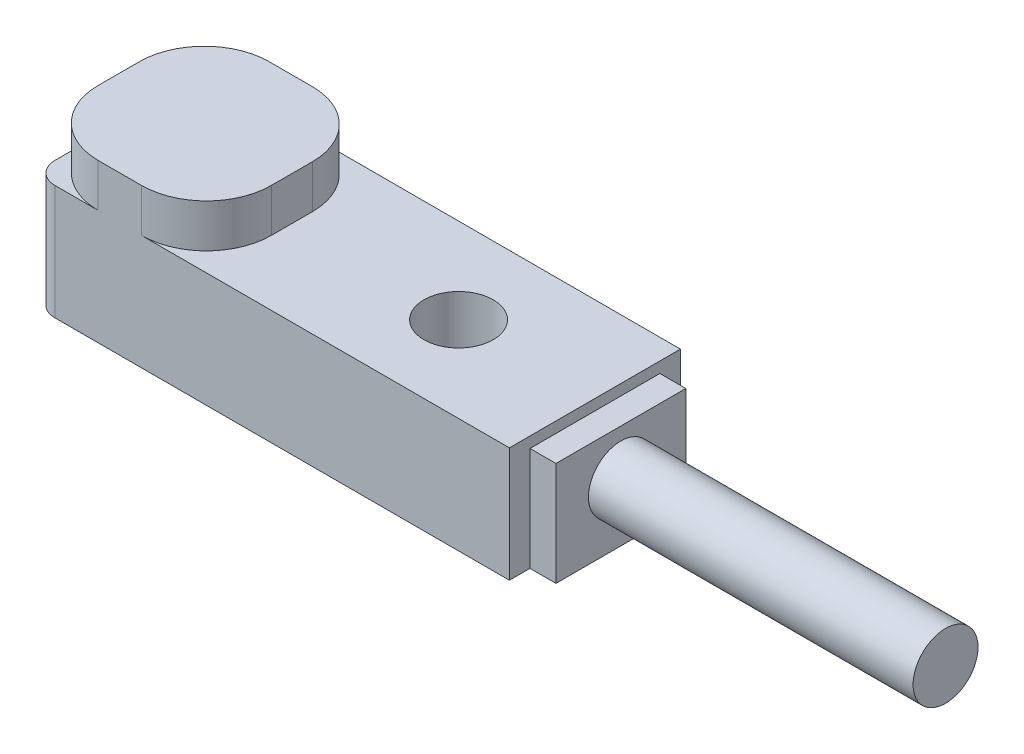
SolidWorks part; units mm, degrees
ref_plane "Plan de face" through (0, 0, 0) normal (0, 0, 1) x (1, 0, 0)
ref_plane "Plan de dessus" through (0, 0, 0) normal (0, 1, 0) x (1, 0, 0)
ref_plane "Plan de droite" through (0, 0, 0) normal (1, 0, 0) x (0, 0, -1)
sketch "Esquisse1" plane through (0, 0, 0) normal (0, 1, 0) x (1, 0, 0)
  line L0 (4, 3.95) -> (18, 3.95)
  line L1 (-4, 3.95) -> (4, 3.95)
  line L2 (-4, 3.95) -> (-4, -3.95)
  line L3 (-4, -3.95) -> (4, -3.95)
  line L4 (4, 3.95) -> (4, -3.95)
  line L5 (18, 3.95) -> (18, -3.95)
  line L6 (18, -3.95) -> (4, -3.95)
  point P4 (-4, 0)
  point P7 (0, 3.95)
  dimension "D1" = 7.9
  dimension "D2" = 8
  dimension "D3" = 22
extrude "Boss.-Extru.1" add sketch "Esquisse1" along normal blind 5.3 contours L6 L5 L0 L4 | L4 L1 L2 L3 region at (0, 0, 0) region at (11, 0, 0)
extrude "Boss.-Extru.2" add sketch "Esquisse1<4>" along normal blind 7.3 contours L4 L1 L2 L3 region at (0, 0, 0)
sketch "Esquisse1<4>" plane through (0, 0, 0) normal (0, 1, 0) x (1, 0, 0) same geometry as "Esquisse1"
sketch "Esquisse2" plane through (0, 7.3, 0) normal (0, 1, 0) x (1, 0, 0)
  line L4 (4, -3.95) -> (4, 3.95)
  line L5 (4, 3.95) -> (-4, 3.95)
  line L6 (-4, 3.95) -> (-4, -3.95)
  line L7 (-4, -3.95) -> (4, -3.95)
  line L8 (4, -0.95) -> (4, 0.95)
  line L9 (1, 3.95) -> (-1, 3.95)
  line L10 (-4, 0.95) -> (-4, -0.95)
  line L11 (-1, -3.95) -> (1, -3.95)
  arc A0 (-4, -0.95) -> (-1, -3.95) centre (-1, -0.95) ccw
  arc A1 (4, -0.95) -> (1, -3.95) centre (1, -0.95) cw
  arc A2 (4, 0.95) -> (1, 3.95) centre (1, 0.95) ccw
  arc A3 (-1, 3.95) -> (-4, 0.95) centre (-1, 0.95) ccw
  dimension "D2" = 3
  dimension "D1" = 0
extrude "Enlèv. mat.-Extru.2" cut sketch "Esquisse2" against normal up to surface (2 mm away) flip side to cut up to face at (11, 5.3, 0)
hole_wizard "Dégagement M31" positions "Esquisse3" profile "Esquisse4" hole size "M3" standard "ISO" end condition through all
sketch "Esquisse3" plane through (0, 5.3, 0) normal (0, 1, 0) x (1, 0, 0)
  point P0 (11.7, 0)
  point P4 (0, 0)
  dimension "D1" = 11.7
sketch "Esquisse4" plane through (11.7, 5.3, 0) normal (1, 0, 0) x (0, 0, 1)
  line L0 (0, 0) -> (0, 5.3)
  line L1 (0, 5.3) -> (1.6, 5.3)
  line L2 (1.6, 5.3) -> (1.6, 0)
  line L5 (1.6, 0) -> (0, 0)
  line L11 (0, -6.35) -> (0, 107.95) construction
  dimension "Diamètre du perçage jusqu'au prochain" = 3.2
  dimension "Profondeur du perçage jusqu'au prochain" = 5.3
fillet "Congé1" radius 1 2 edges at (-4, 2.65, 3.95) (-4, 2.65, -3.95)
sketch "Esquisse5" plane through (18, 0, 0) normal (1, 0, 0) x (0, 0, -1)
  line L0 (3.95, 0) -> (-3.95, 0) construction
  line L1 (-3, 4.8) -> (3, 4.8)
  line L2 (-3, 4.8) -> (-3, 0)
  line L3 (-3, 0) -> (3, 0)
  line L4 (3, 4.8) -> (3, 0)
  point P4 (0, 0)
  point P6 (1.9406, 0)
  dimension "D1" = 6
  dimension "D2" = 4.8
extrude "Boss.-Extru.3" add sketch "Esquisse5" along normal blind 1.2
sketch "Esquisse6" plane through (19.2, 0, 0) normal (1, 0, 0) x (0, 0, -1)
  circle A0 centre (0, 2.7) radius 1.5
  point P2 (0, 0)
  dimension "D2" = 3
  dimension "D1" = 2.7
extrude "Boss.-Extru.4" add sketch "Esquisse6" along normal blind 15
